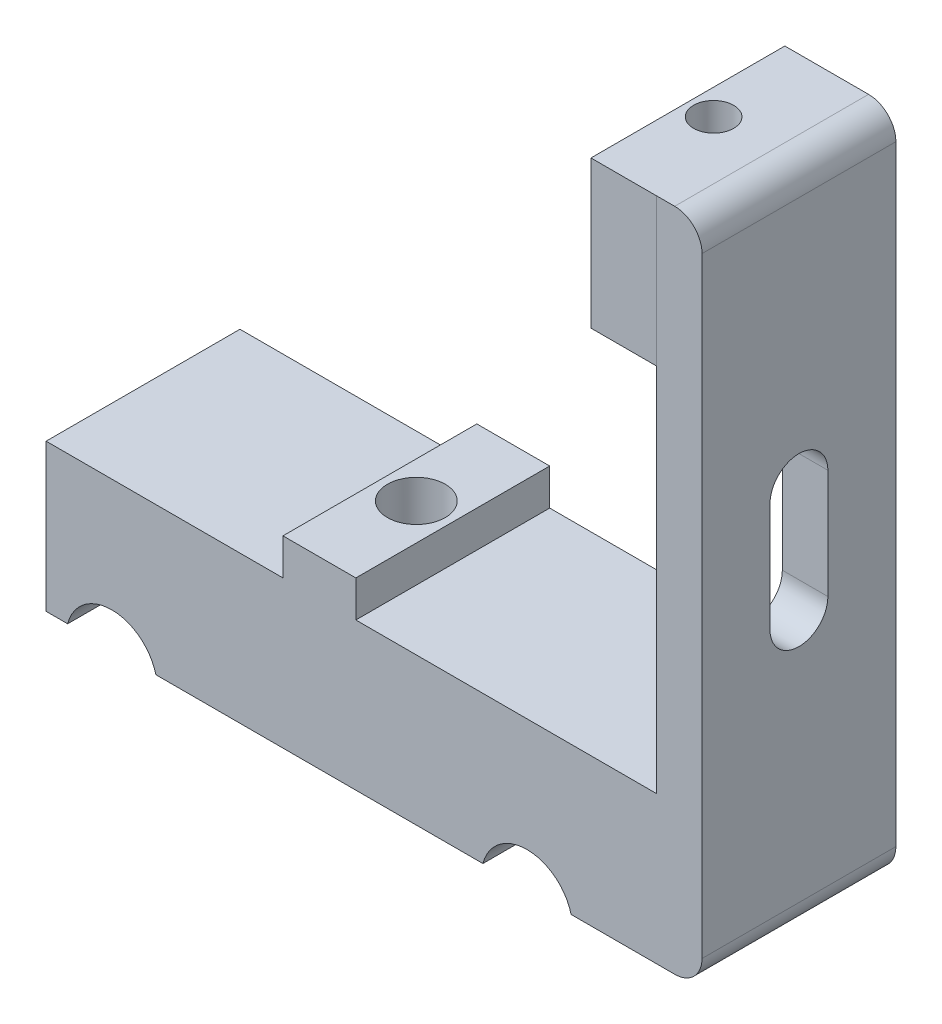
SolidWorks part; units mm, degrees
ref_plane "Front Plane" through (0, 0, 0) normal (0, 0, 1) x (1, 0, 0)
ref_plane "Top Plane" through (0, 0, 0) normal (0, 1, 0) x (1, 0, 0)
ref_plane "Right Plane" through (0, 0, 0) normal (1, 0, 0) x (0, 0, -1)
sketch "Sketch2" plane through (0, 0, 0) normal (0, 0, 1) x (1, 0, 0)
  line L0 (10.1, 0) -> (-10.1, 0)
  line L1 (-10.1, 0) -> (-10.1, 1.7099)
  line L2 (-10.1, 1.7099) -> (-6.2548, 7)
  line L3 (-6.2548, 7) -> (6.2548, 7)
  line L4 (0, 7) -> (0, 0)
  line L5 (0, 0) -> (0, 9.2516) construction
  line L6 (10.1, 1.7099) -> (6.2548, 7)
  line L7 (10.1, 0) -> (10.1, 1.7099)
  dimension "D1" = 20.2
  dimension "D2" = 7
extrude "Boss-Extrude1" add sketch "Sketch2" along normal blind 10.8 contours L4 L3 L2 L1 L0 | L0 L7 L6 L3 L4 region at (4.4168, 3.2082, 0) region at (-4.4168, 3.2082, 0)
sketch "Sketch4" plane through (0, 0, 0) normal (0, 0, 1) x (1, 0, 0)
  line L0 (-4, 0) -> (-4, -4.8)
  line L1 (10.1, 0) -> (-10.1, 0) construction
  line L2 (-4, -4.8) -> (-30, -4.8)
  line L3 (-30, -4.8) -> (-30, -29.8)
  line L4 (-30, -29.8) -> (30, -29.8)
  line L5 (0, 0) -> (0, -29.8) construction
  line L6 (0, -29.8) -> (0, 0)
  line L7 (4, 0) -> (-4, 0)
  line L8 (0, 0) -> (0, -30.5381) construction
  line L9 (30, -4.8) -> (30, -29.8)
  line L10 (4, -4.8) -> (30, -4.8)
  line L11 (4, 0) -> (4, -4.8)
  line L13 (-30, -20.98) -> (30, -20.98)
  line L14 (-30, -20.98) -> (-30, -23.48)
  line L15 (-30, -23.48) -> (30, -23.48)
  line L16 (30, -20.98) -> (30, -23.48)
  dimension "D1" = 4.8
  dimension "D2" = 4
  dimension "D3" = 25
  dimension "D4" = 60
  dimension "D6" = 8.82
extrude "Boss-Extrude2" add sketch "Sketch4" along normal mid plane 21.28 contours L6 L7 L0 L2 L3 L4 | L11 L7 L6 L4 L9 L10 region at (-14.5054, -12.4909, 0) region at (14.5054, -12.4909, 0)
sketch "Sketch5" plane through (0, 0, 0) normal (0, 0, 1) x (1, 0, 0)
  line L0 (-29.791, -22.2274) -> (26.9734, -22.2274) construction
  line L3 (0, -20.98) -> (0, 7) construction
  line L5 (-6.2548, 7) -> (6.2548, 7) construction
  line L20 (-30, -20.98) -> (30, -20.98) construction
  circle A0 centre (-22.791, -22.2274) radius 5
  circle A1 centre (22.791, -22.2274) radius 5
  dimension "D1" = 7
extrude "Cut-Extrude1" cut sketch "Sketch5" along normal through all both and the other way through all
fillet "Fillet1" radius 1 6 edges at (-10.1, 0, 5.4) (-10.1, 1.7099, 5.4) (-6.2548, 7, 5.4) (6.2548, 7, 5.4) (10.1, 0, 5.4) (10.1, 1.7099, 5.4)
sketch "Sketch6" plane through (30, 0, 0) normal (1, 0, 0) x (0, 0, -1)
  line L0 (-10.64, -20.98) -> (10.64, -20.98) construction
  line L1 (-10.64, -4.8) -> (10.64, -4.8)
  line L2 (-10.64, -4.8) -> (-10.64, -20.98)
  line L3 (-10.64, -20.98) -> (10.64, -20.98)
  line L4 (10.64, -4.8) -> (10.64, -20.98)
extrude "Boss-Extrude3" add sketch "Sketch6" along normal blind 12
sketch "Sketch7" plane through (0, -4.8, 0) normal (0, 1, 0) x (1, 0, 0)
  line L0 (4, -10.64) -> (42, -10.64) construction
  line L1 (42, 10.6413) -> (37, 10.6413)
  line L2 (42, 10.6413) -> (42, -10.64)
  line L3 (42, -10.64) -> (37, -10.64)
  line L4 (37, 10.6413) -> (37, -10.64)
  dimension "D1" = 5
extrude "Boss-Extrude4" add sketch "Sketch7" along normal blind 56.83
sketch "Sketch8" plane through (37, 0, 0) normal (-1, 0, 0) x (0, 0, 1)
  line L0 (-10.6413, 52.03) -> (-10.6413, -4.8) construction
  line L1 (10.643, 52.03) -> (-10.6413, 52.03)
  line L2 (10.643, 52.03) -> (10.643, 35.85)
  line L3 (10.643, 35.85) -> (-10.6413, 35.85)
  line L4 (-10.6413, 52.03) -> (-10.6413, 35.85)
  dimension "D1" = 16.18
extrude "Boss-Extrude5" add sketch "Sketch8" along normal blind 7.19
fillet "Fillet3" radius 3 2 edges at (42, 52.03, -0.0007) (42, -20.98, 0)
sketch "Sketch9" plane through (0, -20.98, 0) normal (0, -1, 0) x (1, 0, 0)
  line L0 (27.6329, 0) -> (27.6329, 10.8) construction
  line L2 (27.6329, 10.64) -> (39, 10.64) construction
  circle A0 centre (32.6329, 0) radius 2.2
  dimension "D1" = 5
  dimension "D2" = 10.64
extrude "Cut-Extrude2" cut sketch "Sketch9" against normal through all
sketch "Sketch10" plane through (0, -20.98, 0) normal (0, -1, 0) x (1, 0, 0)
  line L2 (-17.9491, 0) -> (-17.9491, 10.8) construction
  line L3 (-17.9491, 10.64) -> (17.9491, 10.64) construction
  circle A0 centre (0.0009, 0) radius 3.175
  dimension "D1" = 10.64
  dimension "D3" = 6.35
  dimension "D2" = 17.95
extrude "Cut-Extrude3" cut sketch "Sketch10" against normal through all
sketch "Sketch11" plane through (0, 0, 10.8) normal (0, 0, 1) x (1, 0, 0)
  line L0 (9.1, 0) -> (-9.1, 0) construction
  line L1 (-12.6098, 8.9215) -> (12.3675, 8.9215)
  line L2 (-12.6098, 8.9215) -> (-12.6098, -0.8)
  line L3 (-12.6098, -0.8) -> (12.3675, -0.8)
  line L4 (12.3675, 8.9215) -> (12.3675, -0.8)
  dimension "D1" = 0.8
extrude "Cut-Extrude4" cut sketch "Sketch11" against normal through all
sketch "Sketch12" plane through (42, 0, 0) normal (1, 0, 0) x (0, 0, -1)
  line L0 (-3.175, 21.525) -> (-3.175, 9.525)
  line L1 (10.6413, 49.03) -> (-10.64, 49.03) construction
  line L2 (3.175, 9.525) -> (3.175, 21.525)
  arc A0 (3.175, 21.525) -> (-3.175, 21.525) centre (0, 21.525) ccw
  arc A1 (-3.175, 9.525) -> (3.175, 9.525) centre (0, 9.525) ccw
  dimension "D1" = 27.505
  dimension "D2" = 12
extrude "Cut-Extrude5" cut sketch "Sketch12" against normal through all
